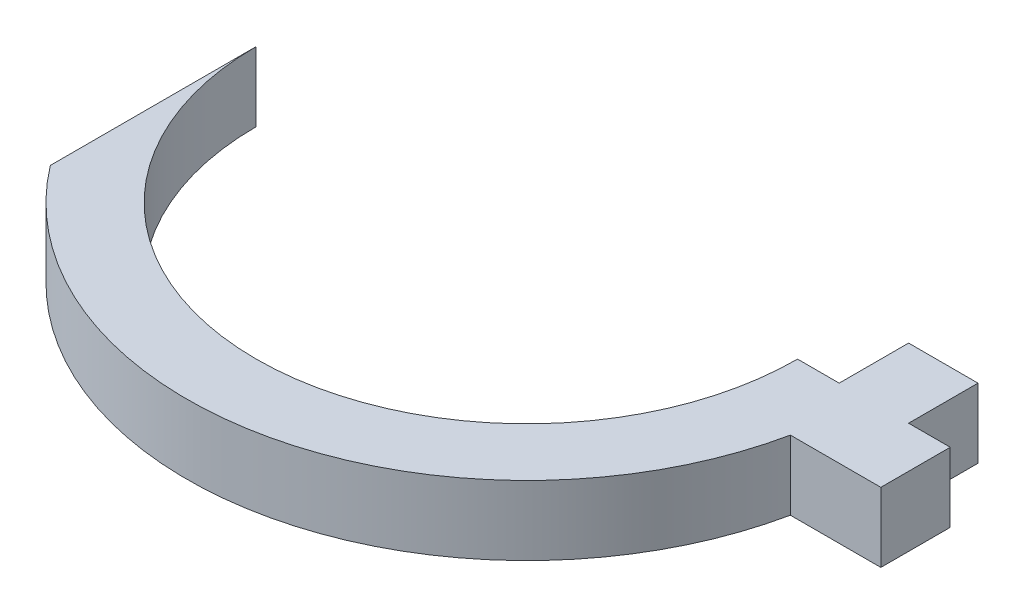
SolidWorks part; units mm, degrees
ref_plane "Front Plane" through (0, 0, 0) normal (0, 0, 1) x (1, 0, 0)
ref_plane "Top Plane" through (0, 0, 0) normal (0, 1, 0) x (1, 0, 0)
ref_plane "Right Plane" through (0, 0, 0) normal (1, 0, 0) x (0, 0, -1)
sketch "Sketch1" plane through (0, 0, 0) normal (0, 1, 0) x (1, 0, 0)
  line L0 (-6.35, -6.35) -> (-6.35, 0)
  line L1 (-6.35, 0) -> (0, 0)
  line L2 (0, 0) -> (0, -6.35)
  line L3 (-6.35, -6.35) -> (-10.16, -6.35)
  line L4 (-59.69, -6.35) -> (-59.69, -25.1871)
  line L5 (0, -6.35) -> (3.81, -6.35)
  line L6 (3.81, -6.35) -> (3.81, -12.7)
  line L7 (3.81, -12.7) -> (-4.4649, -12.7)
  arc A0 (-10.16, -6.35) -> (-59.69, -6.35) centre (-34.925, -6.35) cw
  arc A1 (-59.69, -25.1871) -> (-4.4649, -12.7) centre (-34.925, -6.35) ccw
  dimension "D1" = 24.765
  dimension "D5" = 6.35
  dimension "D4" = 6.35
  dimension "D2" = 3.81
  dimension "D3" = 6.35
  dimension "D6" = 3.81
extrude "Boss-Extrude1" add sketch "Sketch1" along normal blind 6.35
equation "\"Ball Diameter\"= 1.75in"
equation "\"Sheet Thickness\"= 0.25in"
equation "\"Screw Diameter\"= .17in"
equation "\"Robot Diameter\"= 14in"
equation "\"Castor Screw Diameter\"= 0.22in"
equation "\"Wheel Diameter\" = 4in"
equation "\"Nut Diameter\" = 8.4mm"
equation "\"Nut Height\" = 2.9mm"
equation "\"Screw Height\" = 0.55in"
equation "\"Pulley Diameter\" = 1in"
equation "\"Reactor Height\" = 14in"
equation "\"Elevator Height\" = 11.5in"
equation "\"Elevator Width\" = \"Ball Diameter\" + 0.25in"
equation "\"Elevator Bearing Diameter\" = sqr(2*(\"Sheet Thickness\"^2)) + 0.2in"
equation "\"Elevator Axle Endcap Diameter\" = \"Pulley Diameter\" + 0.25in"
equation "\"Elevator Axle Length\" = \"Elevator Width\" + 8*\"Sheet Thickness\""
equation "\"Elevator Clearance from Axis\" = 3.28in"
equation "\"D1@Sketch1\"=\"Ball Radius\" + 0.1in"
equation "\"D3@Sketch1\"=\"Sheet Thickness\""
equation "\"D4@Sketch1\"=\"Sheet Thickness\""
equation "\"D5@Sketch1\"=\"Sheet Thickness\""
equation "\"D1@Boss-Extrude1\"=\"Sheet Thickness\""
equation "\"Ball Radius\" = \"Ball Diameter\"/2"
equation "\"Claw Horizontal Seperation\" = (\"Elevator Width\"/2) - (1.5 * \"Sheet Thickness\") - 0.15in"
